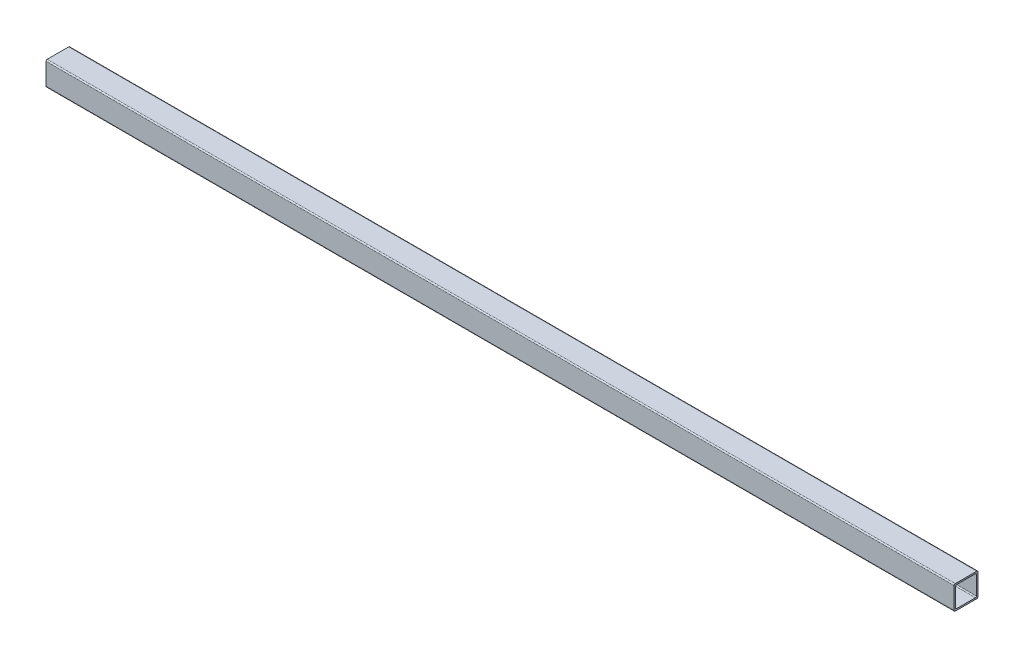
SolidWorks part; units mm, degrees
ref_plane "Front" through (0, 0, 0) normal (0, 0, 1) x (1, 0, 0)
ref_plane "Top" through (0, 0, 0) normal (0, 1, 0) x (1, 0, 0)
ref_plane "Right" through (0, 0, 0) normal (1, 0, 0) x (0, 0, -1)
sketch "Sketch1" plane through (0, 0, 0) normal (1, 0, 0) x (0, 0, -1)
  line L0 (-11.049, 0) -> (-12.7, 0) construction
  line L1 (11.43, -12.7) -> (-11.43, -12.7) construction
  line L2 (12.7, -11.43) -> (12.7, 11.43) construction
  line L3 (11.43, 12.7) -> (-11.43, 12.7) construction
  line L4 (-12.7, -11.43) -> (-12.7, 11.43) construction
  line L5 (12.7, -12.7) -> (-12.7, 12.7) construction
  line L6 (12.7, 12.7) -> (-12.7, -12.7) construction
  line L7 (9.9441, 11.049) -> (-9.9441, 11.049) construction
  line L8 (11.049, 9.9441) -> (11.049, -9.9441) construction
  line L9 (9.9441, -11.049) -> (-9.9441, -11.049) construction
  line L10 (-11.049, 9.9441) -> (-11.049, -9.9441) construction
  line L11 (11.049, 11.049) -> (-11.049, -11.049) construction
  line L12 (11.049, -11.049) -> (-11.049, 11.049) construction
  line L13 (0, -11.049) -> (0, -12.7) construction
  line L14 (11.049, -9.9441) -> (11.049, -12.7) construction
  line L15 (11.049, 0) -> (12.7, 0) construction
  line L16 (11.049, -12.7) -> (12.7, -12.7) construction
  arc A0 (-9.9441, -11.049) -> (-11.049, -9.9441) centre (-9.9441, -9.9441) cw construction
  arc A1 (11.049, -9.9441) -> (9.9441, -11.049) centre (9.9441, -9.9441) cw construction
  arc A2 (9.9441, 11.049) -> (11.049, 9.9441) centre (9.9441, 9.9441) cw construction
  arc A3 (-9.9441, 11.049) -> (-11.049, 9.9441) centre (-9.9441, 9.9441) ccw construction
  arc A4 (11.43, -12.7) -> (12.7, -11.43) centre (11.43, -11.43) ccw construction
  arc A5 (12.7, 11.43) -> (11.43, 12.7) centre (11.43, 11.43) ccw construction
  arc A6 (-11.43, 12.7) -> (-12.7, 11.43) centre (-11.43, 11.43) ccw construction
  arc A7 (-11.43, -12.7) -> (-12.7, -11.43) centre (-11.43, -11.43) cw construction
  point P0 (0, 0)
  point P6 (0, 0)
  dimension "D2" = 1.1049
  dimension "D3" = 1.27
  dimension "Outside Width" = 25.4
  dimension "Ouside Height" = 25.4
  dimension "Inside Height" = 22.098
  dimension "Wall Thickness" = 1.651
sketch "Sketch2" plane through (0, 0, 0) normal (0, 0, 1) x (1, 0, 0)
  line L0 (-482.6, 0) -> (482.6, 0) construction
  point P3 (-458.851, 0)
  point P4 (458.851, 0)
  dimension "Length" = 965.2
  dimension "D1" = 23.749
  dimension "D2" = 23.749
sketch "Sketch4" plane through (0, 0, 0) normal (1, 0, 0) x (0, 0, -1)
  line L8 (12.7, -11.43) -> (12.7, 11.43)
  line L9 (11.43, 12.7) -> (-11.43, 12.7)
  line L10 (-12.7, -11.43) -> (-12.7, 11.43)
  line L11 (11.43, -12.7) -> (-11.43, -12.7)
  line L12 (11.049, 9.9441) -> (11.049, -9.9441)
  line L13 (9.9441, -11.049) -> (-9.9441, -11.049)
  line L14 (-11.049, 9.9441) -> (-11.049, -9.9441)
  line L15 (9.9441, 11.049) -> (-9.9441, 11.049)
  arc A8 (12.7, 11.43) -> (11.43, 12.7) centre (11.43, 11.43) ccw
  arc A9 (-11.43, 12.7) -> (-12.7, 11.43) centre (-11.43, 11.43) ccw
  arc A10 (-12.7, -11.43) -> (-11.43, -12.7) centre (-11.43, -11.43) ccw
  arc A11 (11.43, -12.7) -> (12.7, -11.43) centre (11.43, -11.43) ccw
  arc A12 (9.9441, -11.049) -> (11.049, -9.9441) centre (9.9441, -9.9441) ccw
  arc A13 (-11.049, -9.9441) -> (-9.9441, -11.049) centre (-9.9441, -9.9441) ccw
  arc A14 (-9.9441, 11.049) -> (-11.049, 9.9441) centre (-9.9441, 9.9441) ccw
  arc A15 (11.049, 9.9441) -> (9.9441, 11.049) centre (9.9441, 9.9441) ccw
extrude "Boss-Extrude1" add sketch "Sketch4" along normal up to vertex (-482.6 mm away) and the other way up to vertex (-482.6 mm away) up to point (-482.6, 0, 0) other way up to point (482.6, 0, 0)
equation "\"D3@Sketch1\"=\"Outside Width@Sketch1\"*.05"
equation "\"D2@Sketch1\" = \"Inside Height@Sketch1\" * .05"
equation "\"D1@Sketch2\"=\"Outside Width@Sketch1\"-\"Wall Thickness@Sketch1\""
equation "\"D2@Sketch2\"=\"D1@Sketch2\""
